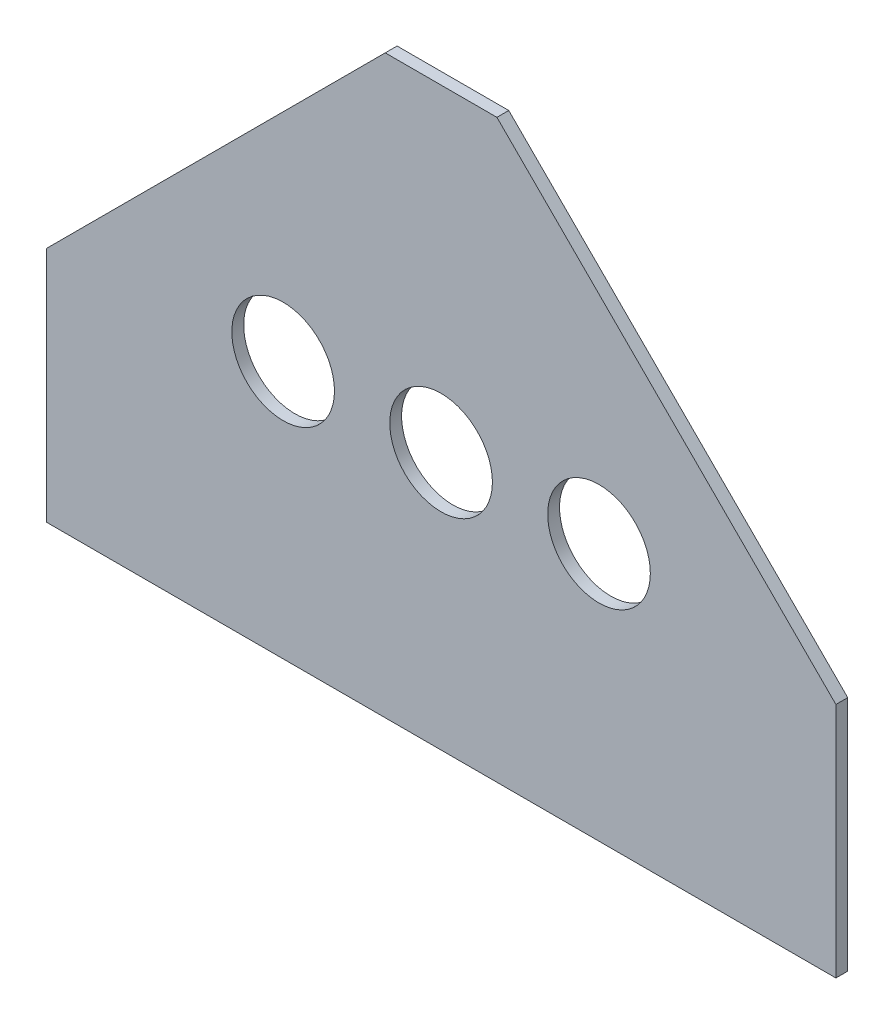
SolidWorks part; units mm, degrees
ref_plane "Спереди" through (0, 0, 0) normal (0, 0, 1) x (1, 0, 0)
ref_plane "Сверху" through (0, 0, 0) normal (0, 1, 0) x (1, 0, 0)
ref_plane "Справа" through (0, 0, 0) normal (1, 0, 0) x (0, 0, -1)
sketch "Эскиз1" plane through (0, 0, 0) normal (0, 0, 1) x (1, 0, 0)
  line L0 (-50, 0) -> (50, 0)
  line L1 (-50, 0) -> (-50, 30)
  line L2 (-50, 30) -> (0, 80)
  line L3 (0, 80) -> (50, 30)
  line L4 (50, 30) -> (50, 0)
  line L5 (0, 0) -> (0, 80) construction
  dimension "D1" = 90
  dimension "D2" = 30
  dimension "D3" = 100
base flange "Базовая кромка1" sketch "Эскиз1" thickness 1.5 reverse thickness direction no parameters "D1"=0.7366
sketch "Эскиз6" plane through (0, 0, 0) normal (0, 0, 1) x (1, 0, 0)
  line L0 (0, 0) -> (0, 32.6238) construction
  line L2 (0, 80) -> (-50, 30) construction
  circle A0 centre (0, 32.6238) radius 6.5
  dimension "D1" = 13
  dimension "D2" = 33.5
extrude "Вырез-Вытянуть1" cut sketch "Эскиз6" against normal blind 10
pattern_linear "Линейный массив1" count 2 spacing 20 along (-1, 0, 0) count 2 spacing 20 along (1, 0, 0) of "Вырез-Вытянуть1"
chamfer "Фаска1" distance 10 angle 45 1 edges at (0, 80, -0.75)
sketch "Сгиб-Линии1" [suppressed] plane through (0, 0, 0) normal (0, 1, 0) x (1, 0, 0)
sketch "Граничная рамка1" [suppressed] plane through (0, 0, 0) normal (0, 1, 0) x (1, 0, 0)
sheet metal parameters "Листовой металл3" thickness 1.5 parameters "D1"=0.7366
flat pattern "Развертка3" [suppressed]
sketch "Сгиб-Линии2" plane through (0, 0, 0) normal (0, 1, 0) x (1, 0, 0)
sketch "Граничная рамка2" [suppressed] plane through (0, 0, 0) normal (0, 1, 0) x (1, 0, 0)
sheet metal parameters "Листовой металл4" thickness 1.5 parameters "D1"=0.7366
flat pattern "Развертка3"
sketch "Сгиб-Линии2" plane through (0, 0, 0) normal (0, 1, 0) x (1, 0, 0)
sketch "Граничная рамка2" [suppressed] plane through (0, 0, 0) normal (0, 1, 0) x (1, 0, 0)
sheet metal parameters "Листовой металл5" thickness 1.5 parameters "D1"=0.7366
flat pattern "Развертка3"
sketch "Сгиб-Линии2" plane through (0, 0, 0) normal (0, 1, 0) x (1, 0, 0)
sketch3d "Граничная рамка2" [suppressed]
  line L0 (-50, 0, 0) -> (50, 0, 0) construction
  line L1 (-50, 72.9289, 0) -> (50, 72.9289, 0) construction
  line L2 (-50, 0, 0) -> (-50, 72.9289, 0) construction
  line L3 (50, 0, 0) -> (50, 72.9289, 0) construction
